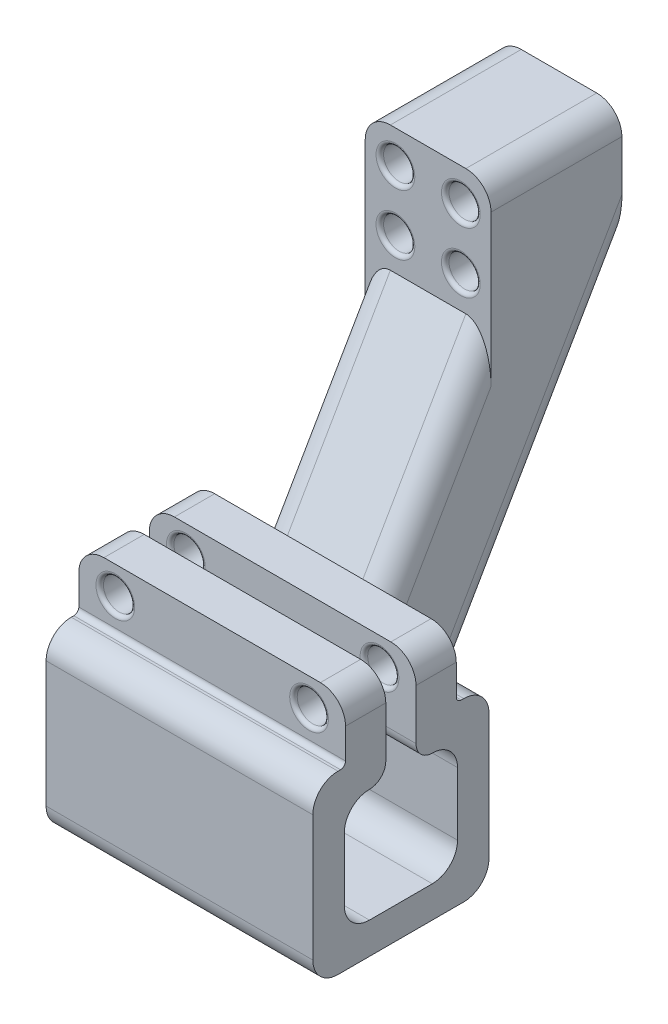
SolidWorks part; units mm, degrees
ref_plane "Front Plane" through (0, 0, 0) normal (0, 0, 1) x (1, 0, 0)
ref_plane "Top Plane" through (0, 0, 0) normal (0, 1, 0) x (1, 0, 0)
ref_plane "Right Plane" through (0, 0, 0) normal (1, 0, 0) x (0, 0, -1)
sketch "Sketch1" plane through (0, 0, 0) normal (1, 0, 0) x (0, 0, -1)
  line L1 (-6.25, -11.25) -> (6.25, -11.25)
  line L2 (-11.25, -6.25) -> (-11.25, 6.25)
  line L3 (-6.25, 11.25) -> (6.25, 11.25)
  line L4 (11.25, -6.25) -> (11.25, 6.25)
  line L5 (-11.25, -11.25) -> (11.25, 11.25) construction
  line L6 (-11.25, 11.25) -> (11.25, -11.25) construction
  line L11 (-17.5, -17.5) -> (17.5, -17.5)
  line L12 (-17.5, -17.5) -> (-17.5, 17.5)
  line L13 (-17.5, 17.5) -> (17.5, 17.5)
  line L14 (17.5, -17.5) -> (17.5, 17.5)
  line L15 (-17.5, -17.5) -> (17.5, 17.5) construction
  line L16 (-17.5, 17.5) -> (17.5, -17.5) construction
  arc A0 (-6.25, -11.25) -> (-11.25, -6.25) centre (-6.25, -6.25) cw
  arc A1 (6.25, -11.25) -> (11.25, -6.25) centre (6.25, -6.25) ccw
  arc A2 (6.25, 11.25) -> (11.25, 6.25) centre (6.25, 6.25) cw
  arc A3 (-11.25, 6.25) -> (-6.25, 11.25) centre (-6.25, 6.25) cw
  point P0 (0, 0)
  point P18 (0, 0)
  point P19 (0, 0)
  dimension "D2" = 5
  dimension "D1" = 22.5
  dimension "D3" = 35
extrude "Boss-Extrude1" add sketch "Sketch1" along normal mid plane 53
fillet "Fillet1" radius 5 3 edges at (0, -17.5, -17.5) (0, -17.5, 17.5) (0, 17.5, 17.5)
sketch "Sketch2" plane through (0, 0, 0) normal (1, 0, 0) x (0, 0, -1)
  line L0 (17.5, 17.5) -> (-12.5, 17.5) construction
  line L1 (17.5, -12.5) -> (17.5, 17.5) construction
  line L2 (17.5, 17.5) -> (-12.5, 17.5)
  line L3 (17.5, -5.5) -> (17.5, 17.5)
  line L4 (17.5, -5.5) -> (57.9145, 64.5)
  line L5 (4.7752, 17.5) -> (31.9107, 64.5)
  line L6 (31.9107, 64.5) -> (57.9145, 64.5)
  point P2 (17.5, -5.134)
  point P3 (0, 0)
  point P7 (0, 0)
  point P8 (14.75, -9.75)
  dimension "D1" = 30
  dimension "D2" = 22.52
  dimension "D3" = 70
  dimension "D4" = 7
extrude "Boss-Extrude2" add sketch "Sketch2" along normal mid plane 25 contours L6 L5 L2 L3 L4 region at (0, 37.5383, -30.2987)
sketch "Sketch3" plane through (0, 64.5, 0) normal (0, 1, 0) x (1, 0, 0)
  line L4 (-12.5, 57.9145) -> (-12.5, 31.9107)
  line L5 (-12.5, 31.9107) -> (12.5, 31.9107)
  line L6 (12.5, 31.9107) -> (12.5, 57.9145)
  line L7 (12.5, 57.9145) -> (-12.5, 57.9145)
  line L8 (-12.5, 57.9145) -> (-12.5, 31.9107)
  line L9 (-12.5, 31.9107) -> (12.5, 31.9107)
  line L10 (12.5, 31.9107) -> (12.5, 57.9145)
  line L11 (12.5, 57.9145) -> (-12.5, 57.9145)
  dimension "D1" = 0
extrude "Boss-Extrude3" add sketch "Sketch3" along normal blind 25
sketch "Sketch4" plane through (0, 17.5, 0) normal (0, 1, 0) x (1, 0, 0)
  line L0 (26.5, 17.5) -> (26.5, -12.5) construction
  line L1 (-26.5, -3) -> (26.5, -3)
  line L2 (-26.5, -3) -> (-26.5, 3)
  line L3 (-26.5, 3) -> (26.5, 3)
  line L4 (26.5, -3) -> (26.5, 3)
  line L5 (-26.5, -3) -> (26.5, 3) construction
  line L6 (-26.5, 3) -> (26.5, -3) construction
  point P0 (0, 0)
  dimension "D1" = 6
extrude "Cut-Extrude1" cut sketch "Sketch4" against normal up to next
sketch "Sketch5" plane through (0, 17.5, 0) normal (0, 1, 0) x (1, 0, 0)
  line L22 (26.5, 3) -> (-26.5, 3) construction
  line L23 (-26.5, 3) -> (26.5, 3)
  line L24 (-26.5, 3) -> (-26.5, 11)
  line L25 (-26.5, 11) -> (26.5, 11)
  line L26 (26.5, 3) -> (26.5, 11)
  line L27 (-26.5, 17.5) -> (-26.5, 3) construction
  line L28 (-19.25, 0) -> (19.25, 0) construction
  line L29 (-26.5, -11) -> (26.5, -11)
  line L30 (26.5, -3) -> (26.5, -11)
  line L31 (-26.5, -3) -> (26.5, -3)
  line L32 (-26.5, -3) -> (-26.5, -11)
  point P6 (0, 3)
  point P7 (-41.5, 8)
  dimension "D1" = 8
extrude "Boss-Extrude4" add sketch "Sketch5" along normal blind 12
sketch "Sketch6" plane through (0, 0, 11) normal (0, 0, 1) x (1, 0, 0)
  line L0 (-26.5, 29.5) -> (-26.5, 17.5) construction
  line L1 (0, -19.25) -> (0, 19.25) construction
  line L2 (-12.5, 89.5) -> (-12.5, 64.5) construction
  line L3 (-12.5, 89.5) -> (12.5, 89.5) construction
  line L6 (-26.5, 29.5) -> (26.5, 29.5) construction
  circle A0 centre (-19.25, 24) radius 3.1
  circle A3 centre (19.25, 24) radius 3.1
  circle A4 centre (-6.5, 83) radius 3.1
  circle A6 centre (-6.5, 71) radius 3.1
  circle A7 centre (6.5, 71) radius 3.1
  circle A8 centre (6.5, 83) radius 3.1
  point P17 (0, 0)
  point P20 (0, 0)
  dimension "D1" = 6.2
  dimension "D3" = 7.25
  dimension "D4" = 6
  dimension "D5" = 12
  dimension "D6" = 6.5
  dimension "D7" = 5.5
extrude "Cut-Extrude2" cut sketch "Sketch6" against normal through all
fillet "Fillet4" radius 1 3 edges at (-19.5, 17.5, -11) (19.5, 17.5, -11) (0, 17.5, 11)
fillet "Fillet2" radius 5 10 edges at (19.5, 17.5, -17.5) (-19.5, 17.5, -17.5) (-26.5, 29.5, -7) (-26.5, 29.5, 7) (26.5, 29.5, -7) (26.5, 29.5, 7) (12.5, 89.5, -44.9126) (-12.5, 89.5, -44.9126) (-12.5, 29.5, -37.7073) (12.5, 29.5, -37.7073)
fillet "Fillet5" radius 3.25 2 edges at (0, 11.25, -3) (0, 11.25, 3)
fillet "Fillet6" radius 0.75 16 edges at (16.15, 24, -3) (-22.35, 24, -3) (-9.6, 71, -31.9107) (-9.6, 83, -31.9107) (3.4, 83, -31.9107) (3.4, 71, -31.9107) (3.4, 71, -57.9145) (-3.4, 71, -57.9145) (-3.4, 83, -57.9145) (3.4, 83, -57.9145) (22.35, 24, -11) (-16.15, 24, -11) (-16.15, 24, 3) (22.35, 24, 3) (16.15, 24, 11) (-16.15, 24, 11)
sketch "Sketch7" plane through (26.5, 0, 0) normal (1, 0, 0) x (0, 0, -1)
  line L0 (0, 0) -> (9.7855, 9.7855)
  line L1 (3, 14.5) -> (3, 24.5) construction
  line L2 (3, 19.5) -> (0, 0)
  line L3 (0, 19.25) -> (0, -19.25) construction
  line L4 (0, 0) -> (-9.7855, 9.7855)
  line L5 (-3, 19.5) -> (0, 0)
  arc A0 (11.25, 6.25) -> (6.25, 11.25) centre (6.25, 6.25) ccw construction
  arc A1 (9.7855, 9.7855) -> (8.8004, 10.5506) centre (6.25, 6.25) ccw
  arc A2 (8.8004, 10.5506) -> (3, 19.5) centre (14.9213, 20.8722) cw
  arc A3 (-8.8004, 10.5506) -> (-3, 19.5) centre (-14.9213, 20.8722) ccw
  arc A4 (-9.7855, 9.7855) -> (-8.8004, 10.5506) centre (-6.25, 6.25) cw
  point P12 (7.566, 11.768)
  point P13 (8.2161, 10.8472)
  point P14 (8.6477, 10.6376)
  point P15 (8.721, 10.5967)
  line M5 (3, 24.5) -> (3, 14.5)
  arc M6 (3, 14.5) -> (6.25, 11.25) centre (6.25, 14.5) ccw
  arc M7 (6.25, 11.25) -> (11.25, 6.25) centre (6.25, 6.25) cw
  arc M13 (-11.25, 6.25) -> (-6.25, 11.25) centre (-6.25, 6.25) cw
  arc M14 (-6.25, 11.25) -> (-3, 14.5) centre (-6.25, 14.5) ccw
  line M15 (-3, 14.5) -> (-3, 24.5)
  dimension "D1" = 12
extrude "Cut-Extrude7" [suppressed] cut sketch "Sketch7" against normal through all contours A3 M13 M14 M15 | A2 M7 M5 M6
sketch "Sketch8" plane through (0, 0, -31.9107) normal (0, 0, 1) x (1, 0, 0)
  line L4 (12.5, 64.5) -> (12.5, 84.5)
  line L5 (7.5, 89.5) -> (-7.5, 89.5)
  line L6 (-12.5, 84.5) -> (-12.5, 64.5)
  line L7 (-12.5, 64.5) -> (12.5, 64.5)
  line L8 (12.5, 64.5) -> (12.5, 84.5)
  line L9 (7.5, 89.5) -> (-7.5, 89.5)
  line L10 (-12.5, 84.5) -> (-12.5, 64.5)
  line L11 (-12.5, 64.5) -> (12.5, 64.5)
  arc A2 (12.5, 84.5) -> (7.5, 89.5) centre (7.5, 84.5) ccw
  arc A3 (-7.5, 89.5) -> (-12.5, 84.5) centre (-7.5, 84.5) ccw
  arc A4 (12.5, 84.5) -> (7.5, 89.5) centre (7.5, 84.5) ccw
  arc A5 (-7.5, 89.5) -> (-12.5, 84.5) centre (-7.5, 84.5) ccw
  dimension "D1" = 0
extrude "Cut-Extrude8" [suppressed] cut sketch "Sketch8" against normal blind 8
fillet "Fillet13" radius 5 2 edges at (12.5, 46.3908, -21.4553) (-12.5, 46.3908, -21.4553)
